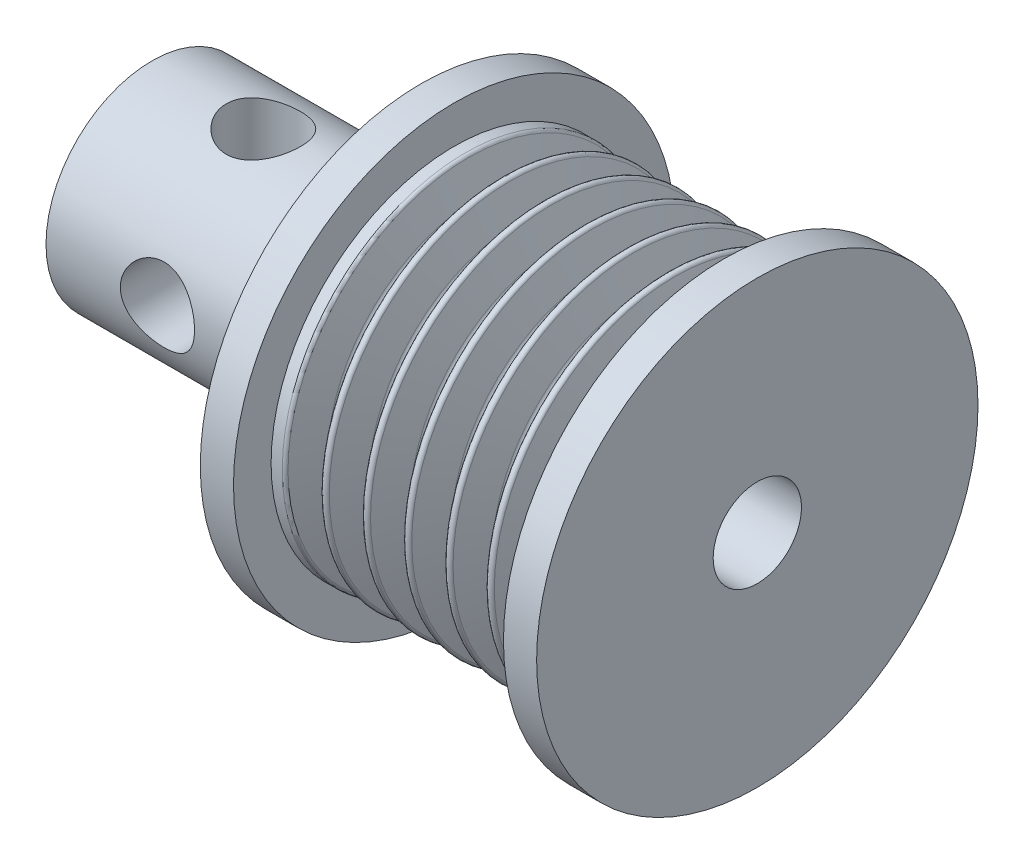
SolidWorks part; units mm, degrees
material "AISI 4130 Steel, annealed at 865C"
ref_plane "Front Plane" through (0, 0, 0) normal (0, 0, 1) x (1, 0, 0)
ref_plane "Top Plane" through (0, 0, 0) normal (0, 1, 0) x (1, 0, 0)
ref_plane "Right Plane" through (0, 0, 0) normal (1, 0, 0) x (0, 0, -1)
sketch "Sketch1" plane through (0, 0, 0) normal (0, 0, 1) x (1, 0, 0)
  line L0 (0, 0) -> (0, 2.5) construction
  line L1 (0, 2.5) -> (34.29, 2.5)
  line L2 (34.29, 2.5) -> (34.29, 12.5)
  line L3 (34.29, 12.5) -> (15.24, 12.5)
  line L4 (15.24, 12.5) -> (15.24, 6)
  line L5 (0, 0) -> (13.5959, 0) construction
  line L8 (15.24, 6) -> (0, 6)
  line L9 (0, 6) -> (0, 2.5)
  point P8 (0, 0)
  dimension "D1" = 25
  dimension "D2" = 5
  dimension "D3" = 19.05
  dimension "D6" = 12
  dimension "D7" = 15.24
revolve "Revolve1" add sketch "Sketch1" angle 360 about L5
sketch "Sketch2" plane through (0, 0, 0) normal (0, 0, 1) x (1, 0, 0)
  line L0 (29.4386, 12.5) -> (29.4386, 10.3699)
  line L1 (15.24, 6) -> (15.24, -6) construction
  line L2 (29.6295, 10.2362) -> (30.2251, 8.5999)
  line L3 (30.9889, 8.5999) -> (31.5845, 10.2362)
  line L4 (31.7754, 10.3699) -> (31.7754, 12.5)
  line L5 (31.7754, 12.5) -> (29.4386, 12.5)
  line L6 (29.4386, 11.43) -> (31.7754, 11.43) construction
  line L7 (15.24, 0) -> (34.29, 0) construction
  line L8 (29.6295, 10.2362) -> (31.5845, 10.2362) construction
  line L9 (29.4386, 12.5) -> (27.1018, 12.5) construction
  line L10 (34.29, 12.5) -> (15.24, 12.5) construction
  line L11 (27.1018, 12.5) -> (24.765, 12.5) construction
  line L13 (24.765, 0) -> (24.765, 12.5) construction
  line L15 (34.29, -12.5) -> (34.29, 12.5) construction
  arc A0 (29.4386, 10.3699) -> (29.6295, 10.2362) centre (29.4386, 10.1667) cw
  arc A1 (30.2251, 8.5999) -> (30.9889, 8.5999) centre (30.607, 8.7389) ccw
  arc A2 (31.5845, 10.2362) -> (31.7754, 10.3699) centre (31.7754, 10.1667) cw
  dimension "D1" = 0.4064
  dimension "D5" = 0.2032
  dimension "D2" = 2.3368
  dimension "D4" = 1.1938
  dimension "D6" = 40
  dimension "D7" = 11.43
revolve "Cut-Revolve1" cut sketch "Sketch2" angle 360 about L7
pattern_linear "LPattern1" count 6 spacing 2.3368 along (-1, 0, 0) of "Cut-Revolve1"
sketch "Sketch3" plane through (0, 0, 0) normal (0, 0, 1) x (1, 0, 0)
  line L0 (31.7754, 12.5) -> (32.4104, 12.5)
  line L1 (34.29, 12.5) -> (31.7754, 12.5) construction
  line L2 (32.4104, 12.5) -> (32.4104, 10.3699)
  line L3 (32.4104, 10.3699) -> (31.7754, 10.3699)
  line L4 (31.7754, 12.5) -> (31.7754, -12.5) construction
  line L5 (31.7754, 10.3699) -> (31.7754, 12.5)
  line L6 (31.7754, 10.3699) -> (31.7754, -10.3699) construction
  line L7 (30.607, 8.3325) -> (30.607, 11.4458) construction
  line L8 (24.765, 10.3699) -> (24.765, 14.7012) construction
  line L9 (17.7546, 10.3699) -> (17.7546, 12.5)
  line L10 (17.1196, 10.3699) -> (17.7546, 10.3699)
  line L11 (17.1196, 12.5) -> (17.1196, 10.3699)
  line L12 (17.7546, 12.5) -> (17.1196, 12.5)
  line L13 (0, 0) -> (26.9583, 0) construction
  arc A0 (30.2251, 8.5999) -> (30.9889, 8.5999) centre (30.607, 8.7389) ccw construction
  arc A1 (24.9559, 10.2362) -> (24.5741, 10.2362) centre (24.765, 10.1667) ccw construction
  dimension "D1" = 1.8034
revolve "Cut-Revolve2" cut sketch "Sketch3" angle 360 about L13
fillet "Fillet1" radius 0.762 1 edges at (15.24, 0, 6)
ref_plane "Plane1" through (0, 6, 0) normal (0, 1, 0) x (1, 0, 0)
hole_wizard "M5x0.8 Tapped Hole1" positions "Sketch6" profile "Sketch5" tap size "M5x0.8" standard "ANSI Metric" end condition up to next
sketch "Sketch6" plane through (0, 6, 0) normal (0, 1, 0) x (1, 0, 0)
  line L1 (6.311, 0) -> (0, 0) construction
  line L7 (9.74, 6) -> (9.74, -6) construction
  line L8 (14.478, 6) -> (0, 6) construction
  line L9 (0, -6) -> (14.478, -6) construction
  line L11 (15.24, 6.762) -> (15.24, -6.762) construction
  circle A0 centre (6.311, 0) radius 3.429 construction
  point P0 (6.311, 0)
  dimension "D1" = 6.858
  dimension "D2" = 5.5
sketch "Sketch5" plane through (6.311, 6, 0) normal (1, 0, 0) x (0, 0, 1)
  line L0 (0, 0) -> (0, 3.5)
  line L1 (0, 3.5) -> (2.1, 3.5)
  line L2 (2.1, 3.5) -> (2.1, 0)
  line L5 (2.1, 0) -> (0, 0)
  line L11 (0, -6.35) -> (0, 107.95) construction
  dimension "Thru Tap Drill Dia." = 4.2
  dimension "Thru Tap Drill Depth" = 3.5
pattern_circular "CirPattern1" count 2 every 90 about axis through (0, 0, 0) along (-1, 0, 0) of "M5x0.8 Tapped Hole1" reverse direction yes
equation "\"D2@Sketch1\"=5mm"
equation "\"D4@Sketch2\"=0.094in/2"
equation "\"D1@Sketch1\"=25mm"
equation "\"D3@Sketch1\"=0.75in"
equation "\"D7@Sketch2\"=0.9in/2"
equation "\"D7@Sketch1\"=0.60in"
equation "\"D2@Sketch6\"=5.5mm"
equation "\"D6@Sketch1\"=12mm"
